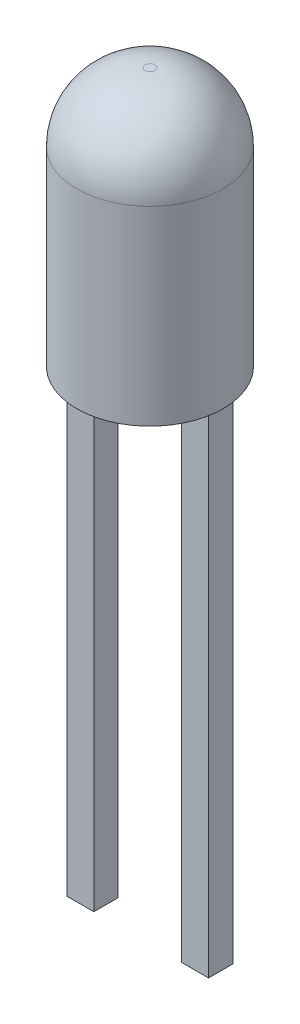
SolidWorks part; units mm, degrees
ref_plane "Front Plane" through (0, 0, 0) normal (0, 0, 1) x (1, 0, 0)
ref_plane "Top Plane" through (0, 0, 0) normal (0, 1, 0) x (1, 0, 0)
ref_plane "Right Plane" through (0, 0, 0) normal (1, 0, 0) x (0, 0, -1)
sketch "Sketch2" plane through (0, 0, 0) normal (0, 1, 0) x (1, 0, 0)
  circle A0 centre (0, 0) radius 1.5
extrude "Boss-Extrude1" add sketch "Sketch2" along normal blind 5.3
fillet "Fillet1" radius 1.4 1 edges at (0, 5.3, 1.5)
sketch "Sketch3" plane through (0, 0, 0) normal (0, 0, 1) x (1, 0, 0)
  line L0 (0, 0) -> (0, 2.6) construction
  line L1 (-1.45, 2.6) -> (1.45, 2.6) construction
  line L2 (-1.45, 2.6) -> (-1.45, 0)
  line L3 (-1.5, 0) -> (1.5, 0) construction
  line L4 (-1.45, 0) -> (-0.9, 0)
  line L5 (-0.9, 0) -> (-0.9, 0.6)
  line L6 (-0.9, 0.6) -> (-0.6241, 0.6)
  line L7 (-0.6241, 0.6) -> (-0.6241, 0.825)
  line L8 (-0.6241, 0.825) -> (-1.2254, 2.6)
  line L9 (-1.2254, 2.6) -> (-1.45, 2.6)
  line L10 (1.45, 2.6) -> (-0.8725, 2.6)
  line L11 (-0.8725, 2.6) -> (0.4967, 0.6)
  line L12 (0.4967, 0.6) -> (0.9, 0.6)
  line L13 (0.9, 0.6) -> (0.9, 0)
  line L14 (0.9, 0) -> (1.45, 0)
  line L15 (1.45, 0) -> (1.45, 2.6)
  line L16 (-0.6241, 0.6) -> (0.4967, 0.6) construction
  line L17 (-0.0637, 0.6) -> (-0.0637, 0) construction
  point P6 (0, 2.6)
extrude "Boss-Extrude2" add sketch "Sketch3" along normal blind 0.25 and the other way blind 0.25 separate body
sketch "Sketch4" plane through (0, 0, 0) normal (0, -1, 0) x (-1, 0, 0)
  line L1 (1.45, -0.25) -> (0.9, -0.25)
  line L2 (1.45, -0.25) -> (1.45, 0.25)
  line L3 (1.45, 0.25) -> (0.9, 0.25)
  line L4 (0.9, -0.25) -> (0.9, 0.25)
  line L5 (-0.9, -0.25) -> (-1.45, -0.25)
  line L6 (-0.9, -0.25) -> (-0.9, 0.25)
  line L7 (-0.9, 0.25) -> (-1.45, 0.25)
  line L8 (-1.45, -0.25) -> (-1.45, 0.25)
extrude "Boss-Extrude3" add sketch "Sketch4" along normal blind 10 separate body
